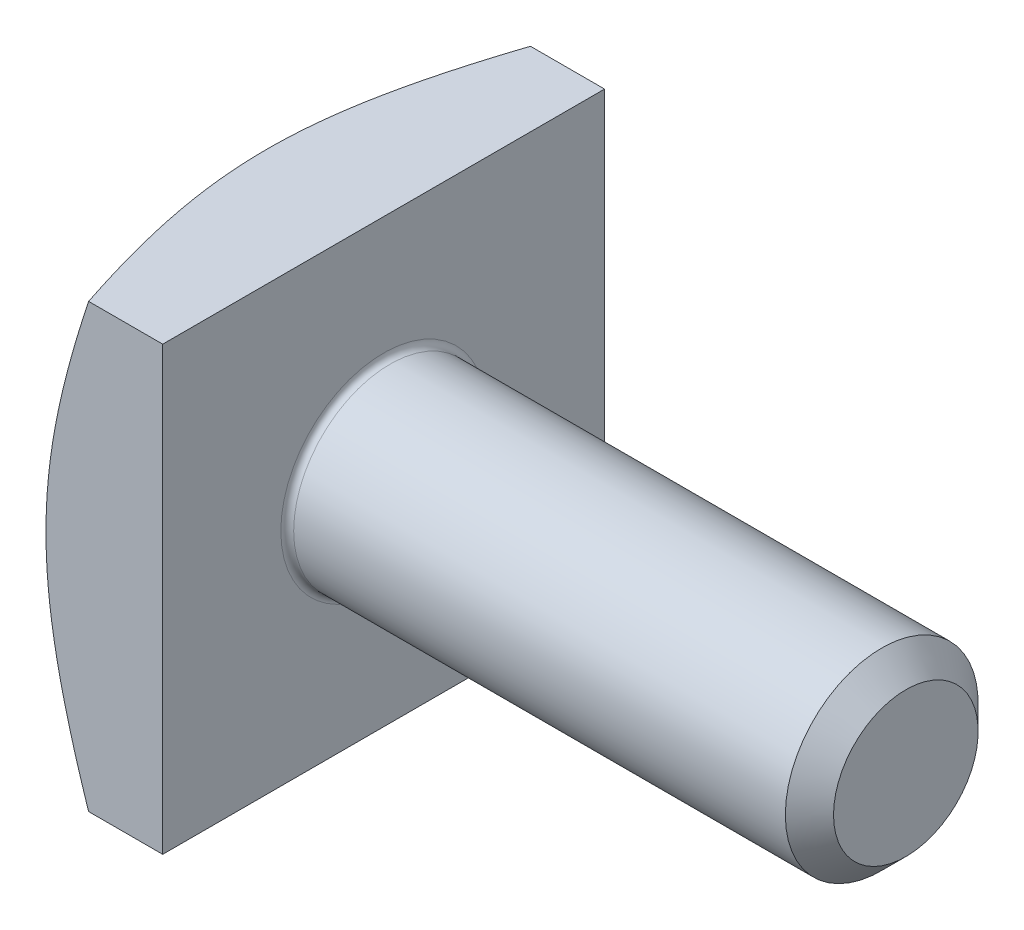
SolidWorks part; units mm, degrees
ref_plane "Front Plane" through (0, 0, 0) normal (0, 0, 1) x (1, 0, 0)
ref_plane "Top Plane" through (0, 0, 0) normal (0, 1, 0) x (1, 0, 0)
ref_plane "Right Plane" through (0, 0, 0) normal (1, 0, 0) x (0, 0, -1)
sketch "BaseHeadSke" plane through (0, 0, 0) normal (1, 0, 0) x (0, 0, -1)
  line L0 (27.5, 27.5) -> (-27.5, -27.5) construction
  line L2 (27.5, 27.5) -> (-27.5, 27.5)
  line L3 (-27.5, 27.5) -> (-27.5, -27.5)
  line L5 (-27.5, -27.5) -> (27.5, -27.5)
  line L6 (27.5, -27.5) -> (27.5, 27.5)
  dimension "Width_flats" = 55
extrude "BaseHead" add sketch "BaseHeadSke" along normal blind 15
sketch "BodySke" plane through (0, 0, 0) normal (0, 0, 1) x (1, 0, 0)
  line L0 (0, 0) -> (80, 0)
  line L1 (80, 0) -> (80, 12)
  line L2 (51.3878, 10.352) -> (123.0174, 10.352) construction
  line L3 (80, 12) -> (0, 12)
  line L4 (0, 12) -> (0, 0)
  line L5 (15, 27.5) -> (15, -27.5) construction
  line L6 (0, 0) -> (159.3976, 0) construction
  line L7 (26, -84.3176) -> (26, 77.7215) construction
  line L8 (77, -21.5941) -> (77, 39.2994) construction
  dimension "Minor_dia" = 20.704
  dimension "Thread_length" = 54
  dimension "Length" = 65
revolve "BaseBody" add sketch "BodySke" angle 360 about L6
cosmetic thread "ThreadCosmetic" [suppressed] parameters "Thread_length"=54, "Thread_minor"=20.704
sketch "ChamferEndSke" plane through (0, 0, 0) normal (0, 1, 0) x (1, 0, 0)
  line L0 (77, -12) -> (80, -9)
  line L1 (80, -9) -> (80, -12)
  line L2 (80, -12) -> (77, -12)
  line L4 (80, -12) -> (80, 12) construction
  line L5 (15, -12) -> (80, -12) construction
  line L6 (0, 0) -> (120.8692, 0) construction
  dimension "Ang" = 45
revolve "ChamferEnd" cut sketch "ChamferEndSke" angle 360 about L6
sketch "CutEndSke" plane through (80, 0, 0) normal (1, 0, 0) x (0, 0, -1)
  circle A0 centre (0, 0) radius 12 construction
  circle A1 centre (0, 0) radius 12
extrude "CutEnd" [suppressed] cut sketch "CutEndSke" against normal blind 3
dome "RoundEnd" [suppressed] faces to dome 1 distance 3 parameters "D1"=3
sketch "HeadChamferSke" plane through (0, 0, 0) normal (0, 0, 1) x (1, 0, 0)
  line L0 (15, 58.6676) -> (0, 58.6676)
  line L1 (0, 58.6676) -> (0, 26.5)
  line L2 (0, 26.5) -> (15, 58.6676)
  line L3 (0, 0) -> (120.9185, 0) construction
  dimension "D1" = 25
  dimension "Head_chamfer" = 53
revolve "HeadChamfer" cut sketch "HeadChamferSke" angle 360 about L3
fillet "Fillet" radius 0.8 1 edges at (15, 0, 12)
sketch "ThdSchSke" plane through (0, 0, 0) normal (0, 0, 1) x (1, 0, 0)
  line L0 (74.5485, 13.9029) -> (74.5485, 12)
  line L1 (74.5485, 12) -> (75.5, 10.352)
  line L2 (75.5, 10.352) -> (76.4515, 12)
  line L3 (76.4515, 12) -> (76.4515, 13.9029)
  line L4 (76.4515, 13.9029) -> (74.5485, 13.9029)
  line L6 (0, 0) -> (141.9934, 0) construction
  line L8 (80, -61.7617) -> (80, 46.755) construction
  line L9 (15, -27.5) -> (15, 27.5) construction
  dimension "D2" = 20.704
  dimension "D3" = 24
  dimension "Length" = 65
  dimension "Advance" = 4.5
revolve "ThreadSchematic" [suppressed] cut sketch "ThdSchSke" angle 360 about L6
pattern_linear "ThdSchPat" [suppressed] count 18 spacing 3 along (-1, 0, 0) of bodies 107
equation "\"Thread_minor@ThreadCosmetic\" = \"Minor_dia@BodySke\""
equation "\"Thread_length@ThreadCosmetic\" = \"Thread_length@BodySke\""
equation "\"D1@CutEnd\" = \"Chamfer_width@ChamferEndSke\""
equation "\"D1@RoundEnd\" = \"Chamfer_width@ChamferEndSke\""
equation "\"D2@ThdSchSke\" = \"Minor_dia@BodySke\""
equation "\"D3@ThdSchSke\" = \"Diameter@BodySke\""
equation "\"Length@ThdSchSke\" = \"Length@BodySke\""
equation "\"Advance@ThdSchSke\" = \"Advance@BodySke\"*1.5"
equation "\"D3@ThdSchPat\" = \"Advance@BodySke\""
equation "\"D1@ThdSchPat\" =  int( \"Thread_length@BodySke\"/\"Advance@BodySke\" )"
